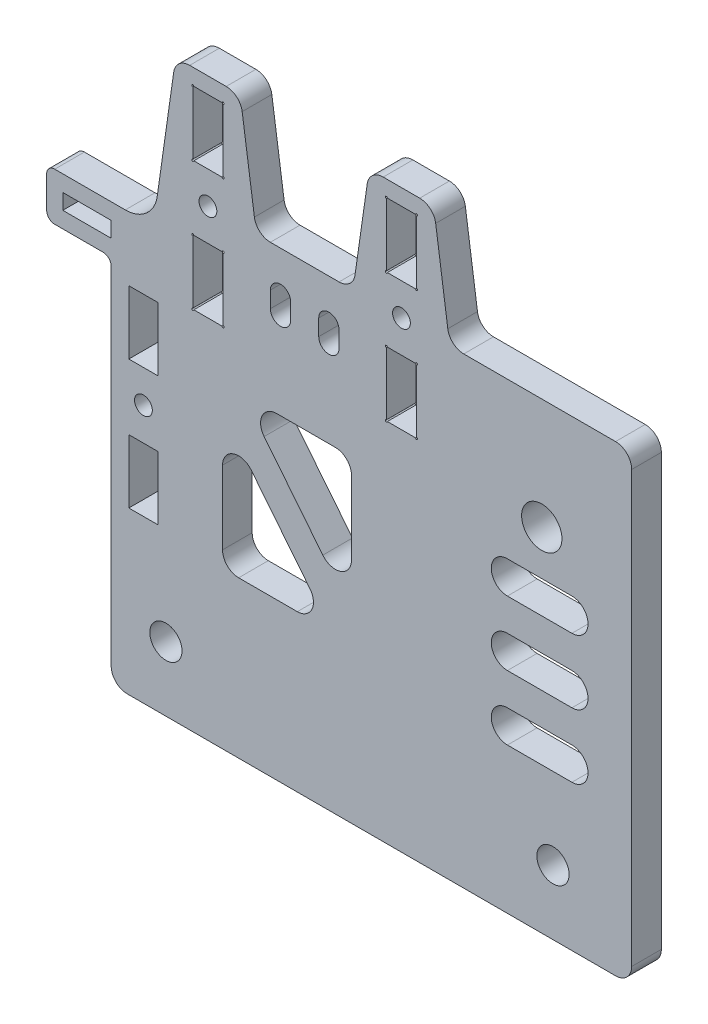
SolidWorks part; units mm, degrees
ref_plane "Front Plane" through (0, 0, 0) normal (0, 0, 1) x (1, 0, 0)
ref_plane "Top Plane" through (0, 0, 0) normal (0, 1, 0) x (1, 0, 0)
ref_plane "Right Plane" through (0, 0, 0) normal (1, 0, 0) x (0, 0, -1)
sketch "Sketch1" plane through (0, 0, 0) normal (0, 0, 1) x (1, 0, 0)
  line L0 (-40.2246, 5.8803) -> (-40.2246, -38.4697) construction
  line L1 (51.8504, -38.4697) -> (-46.5746, -38.4697)
  line L3 (-46.5746, 34.5553) -> (-46.5746, 52.6159)
  line L4 (-46.5746, -38.4697) -> (-46.5746, 34.5553)
  line L5 (51.8504, -38.4697) -> (-46.5746, 34.5553) construction
  line L6 (42.1271, 34.7961) -> (-46.5746, -38.4697) construction
  line L7 (-43.0956, -6.6197) -> (-37.3536, -6.6197)
  line L8 (-43.0956, 18.7803) -> (-37.3536, 18.7803)
  line L9 (-43.0956, 18.7803) -> (-43.0956, 31.2803)
  line L10 (-43.0956, 31.2803) -> (-37.3536, 31.2803)
  line L11 (-37.3536, 18.7803) -> (-37.3536, 31.2803)
  line L12 (-43.0956, 18.7803) -> (-37.3536, 31.2803) construction
  line L13 (-43.0956, 31.2803) -> (-37.3536, 18.7803) construction
  line L14 (-43.0956, -6.6197) -> (-43.0956, 5.8803)
  line L15 (-43.0956, 5.8803) -> (-37.3536, 5.8803)
  line L16 (-37.3536, -6.6197) -> (-37.3536, 5.8803)
  line L17 (-43.0956, -6.6197) -> (-37.3536, 5.8803) construction
  line L18 (-43.0956, 5.8803) -> (-37.3536, -6.6197) construction
  line L19 (-46.5746, 52.6159) -> (51.8504, 52.6159)
  line L20 (51.8504, -25.7697) -> (-46.5746, -25.7697) construction
  line L21 (-40.2246, -0.3697) -> (-40.2246, 25.0303) construction
  line L24 (51.8504, 52.6159) -> (55.8972, 52.6159)
  line L26 (51.8504, -38.4697) -> (55.8972, -38.4697)
  line L27 (55.8972, 52.6159) -> (55.8972, -38.4697)
  circle A0 centre (-35.7968, -25.7697) radius 3.175
  circle A1 centre (40.4032, -25.7697) radius 3.175
  circle A2 centre (-40.2246, 12.3303) radius 1.7526
  point P0 (0, 0)
  point P8 (-40.2246, 25.0303)
  point P14 (-40.2246, -0.3697)
  dimension "D10" = 6.35
  dimension "D13" = 3.5052
  dimension "D1" = 98.425
  dimension "D2" = 73.025
  dimension "D3" = 5.742
  dimension "D4" = 12.5
  dimension "D6" = 6.35
  dimension "D7" = 18.0606
  dimension "D8" = 15.494
  dimension "D12" = 10.7778
  dimension "D5" = 2
  dimension "D11" = 2
extrude "Boss-Extrude1" add sketch "Sketch1" along normal blind 5.842
sketch "Sketch2" plane through (0, 0, 5.842) normal (0, 0, 1) x (1, 0, 0)
  line L0 (55.8972, -38.4697) -> (55.8972, 52.6159) construction
  line L1 (-46.5746, -38.4697) -> (55.8972, -38.4697) construction
  line L2 (33.2912, 44.7153) -> (43.1972, 44.7153) construction
  line L3 (33.2912, -3.5447) -> (43.1972, -3.5447) construction
  line L4 (38.2442, -3.5447) -> (38.2442, 44.7153) construction
  line L6 (48.0747, 0.1423) -> (28.4136, 0.1423)
  line L7 (48.2732, 0.3408) -> (48.2732, 40.8299)
  line L8 (48.0747, 41.0283) -> (28.4136, 41.0283)
  line L9 (28.2152, 0.3408) -> (28.2152, 40.8299)
  line L10 (48.2732, 0.1423) -> (28.2152, 41.0283) construction
  line L11 (48.2732, 41.0283) -> (28.2152, 0.1423) construction
  circle A0 centre (43.1972, -3.5447) radius 1.7526
  circle A1 centre (33.2912, -3.5447) radius 1.7526
  circle A2 centre (43.1972, 44.7153) radius 1.7526
  circle A3 centre (33.2912, 44.7153) radius 1.7526
  arc A4 (48.0747, 0.1423) -> (48.2732, 0.3408) centre (48.2732, 0.1423) ccw
  arc A5 (48.2732, 40.8299) -> (48.0747, 41.0283) centre (48.2732, 41.0283) ccw
  arc A6 (28.2152, 40.8299) -> (28.4136, 41.0283) centre (28.2152, 41.0283) cw
  arc A7 (28.4136, 0.1423) -> (28.2152, 0.3408) centre (28.2152, 0.1423) cw
  point P14 (38.2442, 20.5853)
  dimension "D1" = 3.5052
  dimension "D6" = 0.3969
  dimension "D7" = 0.3969
  dimension "D2" = 12.7
  dimension "D3" = 34.925
  dimension "D4" = 20.058
  dimension "D5" = 40.886
extrude "Cut-Extrude1" [suppressed] cut sketch "Sketch2" against normal through all
sketch "Sketch3" plane through (0, 0, 5.842) normal (0, 0, 1) x (1, 0, 0)
  line L0 (-46.5746, 39.9159) -> (55.8972, 39.9159) construction
  line L1 (-46.5746, 52.6159) -> (-46.5746, -38.4697) construction
  line L2 (55.8972, -38.4697) -> (55.8972, 52.6159) construction
  line L3 (55.8972, 52.6159) -> (-46.5746, 52.6159) construction
  line L4 (7.5909, 46.2659) -> (13.5599, 33.5659) construction
  line L5 (-24.7385, 33.5659) -> (-30.3106, 33.5659)
  line L6 (-24.5401, 33.7644) -> (-24.5401, 46.0675)
  line L7 (-24.7385, 46.2659) -> (-30.3106, 46.2659)
  line L8 (-30.5091, 33.7644) -> (-30.5091, 46.0675)
  line L9 (-24.5401, 33.5659) -> (-30.5091, 46.2659) construction
  line L10 (-8.4746, 52.6159) -> (-8.4746, 39.9159) construction
  line L11 (-24.5401, 46.2659) -> (-30.5091, 33.5659) construction
  line L12 (7.5909, 33.5659) -> (13.5599, 46.2659) construction
  line L13 (13.5599, 33.7644) -> (13.5599, 46.0675)
  line L14 (7.7894, 46.2659) -> (13.3615, 46.2659)
  line L15 (7.5909, 33.7644) -> (7.5909, 46.0675)
  line L16 (7.7894, 33.5659) -> (13.3615, 33.5659)
  arc A0 (-24.7385, 33.5659) -> (-24.5401, 33.7644) centre (-24.5401, 33.5659) ccw
  arc A1 (-30.5091, 33.7644) -> (-30.3106, 33.5659) centre (-30.5091, 33.5659) ccw
  arc A2 (-24.7385, 46.2659) -> (-24.5401, 46.0675) centre (-24.5401, 46.2659) cw
  arc A3 (-30.5091, 46.0675) -> (-30.3106, 46.2659) centre (-30.5091, 46.2659) cw
  arc A4 (13.5599, 46.0675) -> (13.3615, 46.2659) centre (13.5599, 46.2659) ccw
  arc A5 (7.7894, 46.2659) -> (7.5909, 46.0675) centre (7.5909, 46.2659) ccw
  arc A6 (13.5599, 33.7644) -> (13.3615, 33.5659) centre (13.5599, 33.5659) cw
  arc A7 (7.7894, 33.5659) -> (7.5909, 33.7644) centre (7.5909, 33.5659) cw
  point P6 (-27.5246, 39.9159)
  point P7 (-27.5246, 39.9159)
  point P39 (10.5754, 39.9159)
  dimension "D3" = 0.3969
  dimension "D4" = 0.3969
  dimension "D1" = 5.969
  dimension "D2" = 12.7
  dimension "D5" = 12.7
  dimension "D6" = 19.05
  dimension "D9" = 19.05
extrude "Cut-Extrude2" cut sketch "Sketch3" against normal through all
sketch "Sketch4" plane through (0, 0, 5.842) normal (0, 0, 1) x (1, 0, 0)
  line L0 (-30.5091, 39.9159) -> (13.5599, 39.9159) construction
  line L3 (10.5754, 39.9159) -> (10.5754, 65.3159) construction
  line L4 (-8.4746, 39.9159) -> (-8.4746, 46.2659) construction
  line L5 (1.0366, 52.6159) -> (4.2254, 74.8409)
  line L6 (13.3615, 71.6659) -> (7.7894, 71.6659)
  line L7 (13.5599, 71.4675) -> (13.5599, 59.1644)
  line L8 (13.3615, 58.9659) -> (7.7894, 58.9659)
  line L9 (7.5909, 71.4675) -> (7.5909, 59.1644)
  line L10 (13.5599, 71.6659) -> (7.5909, 58.9659) construction
  line L11 (13.5599, 58.9659) -> (7.5909, 71.6659) construction
  line L12 (55.8972, 52.6159) -> (-46.5746, 52.6159) construction
  line L13 (4.2254, 74.8409) -> (16.9254, 74.8409)
  line L14 (16.9254, 74.8409) -> (20.0866, 52.6159)
  line L15 (20.0866, 52.6159) -> (1.0366, 52.6159)
  line L16 (-30.5091, 58.9659) -> (-24.5401, 71.6659) construction
  line L17 (-30.5091, 71.6659) -> (-24.5401, 58.9659) construction
  line L18 (-37.0358, 52.6159) -> (-17.9858, 52.6159)
  line L19 (-33.8746, 74.8409) -> (-37.0358, 52.6159)
  line L20 (-21.1746, 74.8409) -> (-33.8746, 74.8409)
  line L21 (-24.5401, 71.4675) -> (-24.5401, 59.1644)
  line L22 (-30.3106, 58.9659) -> (-24.7385, 58.9659)
  line L23 (-30.5091, 71.4675) -> (-30.5091, 59.1644)
  line L24 (-30.3106, 71.6659) -> (-24.7385, 71.6659)
  line L25 (-17.9858, 52.6159) -> (-21.1746, 74.8409)
  line L26 (13.5599, 33.7644) -> (13.5599, 46.0675) construction
  line L27 (-30.5091, 46.0675) -> (-30.5091, 33.7644) construction
  arc A0 (13.5599, 71.4675) -> (13.3615, 71.6659) centre (13.5599, 71.6659) ccw
  arc A1 (13.3615, 58.9659) -> (13.5599, 59.1644) centre (13.5599, 58.9659) ccw
  arc A2 (7.7894, 58.9659) -> (7.5909, 59.1644) centre (7.5909, 58.9659) cw
  arc A3 (7.5909, 71.4675) -> (7.7894, 71.6659) centre (7.5909, 71.6659) cw
  arc A4 (-24.5401, 71.4675) -> (-24.7385, 71.6659) centre (-24.5401, 71.6659) ccw
  arc A5 (-30.5091, 71.4675) -> (-30.3106, 71.6659) centre (-30.5091, 71.6659) cw
  arc A6 (-24.7385, 58.9659) -> (-24.5401, 59.1644) centre (-24.5401, 58.9659) ccw
  arc A7 (-30.3106, 58.9659) -> (-30.5091, 59.1644) centre (-30.5091, 58.9659) cw
  point P20 (10.5754, 74.8409)
  point P29 (-27.5246, 74.8409)
  dimension "D7" = 0.3969
  dimension "D8" = 0.3969
  dimension "D1" = 25.4
  dimension "D2" = 12.7
  dimension "D3" = 5.969
  dimension "D4" = 9.525
  dimension "D5" = 12.7
  dimension "D6" = 19.05
extrude "Boss-Extrude2" add sketch "Sketch4" against normal up to surface (5.842 mm away) up to face at (10.5754, 39.9159, 0)
fillet "Fillet1" radius 3.175 7 edges at (16.9254, 74.8409, 2.921) (4.2254, 74.8409, 2.921) (-17.9858, 52.6159, 2.921) (-21.1746, 74.8409, 2.921) (-33.8746, 74.8409, 2.921)
sketch "Sketch5" plane through (0, 0, 5.842) normal (0, 0, 1) x (1, 0, 0)
  line L0 (-27.5246, 71.6659) -> (-27.5246, 33.5659) construction
  line L1 (-24.7385, 71.6659) -> (-30.3106, 71.6659) construction
  line L2 (-30.3106, 33.5659) -> (-24.7385, 33.5659) construction
  line L3 (10.5754, 71.6659) -> (10.5754, 33.5659) construction
  line L4 (13.3615, 71.6659) -> (7.7894, 71.6659) construction
  line L5 (7.7894, 33.5659) -> (13.3615, 33.5659) construction
  circle A0 centre (-27.5246, 52.6159) radius 1.7526
  circle A1 centre (10.5754, 52.6159) radius 1.7526
  dimension "D1" = 3.5052
  dimension "D2" = 3.5052
extrude "Cut-Extrude3" cut sketch "Sketch5" against normal through all
sketch "Sketch6" plane through (0, 0, 5.842) normal (0, 0, 1) x (1, 0, 0)
  line L0 (-37.0358, 52.6159) -> (-39.1672, 37.6303)
  line L1 (-34.2626, 72.113) -> (-37.0358, 52.6159) construction
  line L2 (-37.3536, 31.2803) -> (-43.0956, 31.2803) construction
  line L3 (-39.1672, 37.6303) -> (-46.5746, 37.6303)
  line L4 (-46.5746, 52.6159) -> (-46.5746, -38.4697) construction
  line L5 (-46.5746, 37.6303) -> (-46.5746, 52.6159)
  line L6 (-46.5746, 52.6159) -> (-37.0358, 52.6159)
  dimension "D1" = 6.35
extrude "Cut-Extrude4" cut sketch "Sketch6" against normal through all
fillet "Fillet2" radius 3.175 5 edges at (-39.1672, 37.6303, 2.921) (-46.5746, 37.6303, 2.921) (-46.5746, -38.4697, 2.921) (55.8972, 52.6159, 2.921) (55.8972, -38.4697, 2.921)
sketch "Sketch7" [suppressed] plane through (0, 0, 5.842) normal (0, 0, 1) x (1, 0, 0)
  line L0 (6.4764, -22.5947) -> (19.1764, -22.5947) construction
  line L1 (6.4764, -19.4197) -> (19.1764, -19.4197)
  line L2 (6.4764, -25.7697) -> (19.1764, -25.7697)
  line L3 (-43.3996, -38.4697) -> (52.7222, -38.4697) construction
  arc A0 (6.4764, -19.4197) -> (6.4764, -25.7697) centre (6.4764, -22.5947) ccw
  arc A1 (19.1764, -25.7697) -> (19.1764, -19.4197) centre (19.1764, -22.5947) ccw
  point P2 (12.8264, -22.5947)
  dimension "D3" = 3.175
  dimension "D1" = 12.7
  dimension "D2" = 12.7
extrude "Cut-Extrude5" [suppressed] cut sketch "Sketch7" against normal through all
sketch "Sketch8" [suppressed] plane through (0, 0, 5.842) normal (0, 0, 1) x (1, 0, 0)
  line L0 (17.7972, -38.4697) -> (17.7972, 37.7303) construction
  line L1 (-43.3996, -38.4697) -> (52.7222, -38.4697) construction
  line L2 (55.8972, -35.2947) -> (55.8972, 49.4409) construction
  line L3 (14.6222, 5.9803) -> (20.9722, 5.9803) construction
  line L4 (14.6222, 7.5678) -> (20.9722, 7.5678)
  line L5 (14.6222, 4.3928) -> (20.9722, 4.3928)
  line L6 (14.6222, 25.0303) -> (20.9722, 25.0303) construction
  line L7 (14.6222, 26.6178) -> (20.9722, 26.6178)
  line L8 (14.6222, 23.4428) -> (20.9722, 23.4428)
  arc A0 (14.6222, 7.5678) -> (14.6222, 4.3928) centre (14.6222, 5.9803) ccw
  arc A1 (20.9722, 4.3928) -> (20.9722, 7.5678) centre (20.9722, 5.9803) ccw
  arc A2 (14.6222, 26.6178) -> (14.6222, 23.4428) centre (14.6222, 25.0303) ccw
  arc A3 (20.9722, 23.4428) -> (20.9722, 26.6178) centre (20.9722, 25.0303) ccw
  point P8 (17.7972, 5.9803)
  point P17 (17.7972, 25.0303)
  dimension "D2" = 1.5875
  dimension "D1" = 38.1
  dimension "D3" = 6.35
  dimension "D4" = 76.2
  dimension "D5" = 2
  dimension "D6" = 44.45
extrude "Cut-Extrude6" [suppressed] cut sketch "Sketch8" against normal through all
sketch "Sketch9" [suppressed] plane through (0, 0, 5.842) normal (0, 0, 1) x (1, 0, 0)
  line L0 (3.3014, -22.5947) -> (-46.5746, -22.5947) construction
  line L1 (-46.5746, 34.4553) -> (-46.5746, -35.2947) construction
  line L2 (-15.7486, -25.7697) -> (-15.7486, -19.4197) construction
  line L3 (-17.3361, -25.7697) -> (-17.3361, -19.4197)
  line L4 (-14.1611, -25.7697) -> (-14.1611, -19.4197)
  line L5 (-3.0486, -25.7697) -> (-3.0486, -19.4197) construction
  line L6 (-4.6361, -25.7697) -> (-4.6361, -19.4197)
  line L7 (-1.4611, -25.7697) -> (-1.4611, -19.4197)
  arc A0 (6.4764, -19.4197) -> (6.4764, -25.7697) centre (6.4764, -22.5947) ccw construction
  arc A1 (-17.3361, -25.7697) -> (-14.1611, -25.7697) centre (-15.7486, -25.7697) ccw
  arc A2 (-14.1611, -19.4197) -> (-17.3361, -19.4197) centre (-15.7486, -19.4197) ccw
  arc A3 (-4.6361, -25.7697) -> (-1.4611, -25.7697) centre (-3.0486, -25.7697) ccw
  arc A4 (-1.4611, -19.4197) -> (-4.6361, -19.4197) centre (-3.0486, -19.4197) ccw
  point P10 (-15.7486, -22.5947)
  point P18 (-3.0486, -22.5947)
  dimension "D2" = 1.5875
  dimension "D1" = 6.35
  dimension "D3" = 19.05
extrude "Cut-Extrude7" [suppressed] cut sketch "Sketch9" against normal through all
sketch "Sketch10" plane through (0, 0, 5.842) normal (0, 0, 1) x (1, 0, 0)
  line L0 (-20.5876, 24.0409) -> (0.7464, 24.0409)
  line L1 (-30.3106, 33.5659) -> (-24.7385, 33.5659) construction
  line L2 (-24.6536, 18.9584) -> (-24.6536, -7.7091)
  line L3 (-37.3536, 18.7803) -> (-37.3536, 31.2803) construction
  line L4 (0.7464, 24.0409) -> (0.7464, -2.6266)
  line L5 (-3.3196, -7.7091) -> (-24.6536, -7.7091)
  line L7 (-24.6536, 18.9584) -> (-3.3196, -7.7091)
  line L8 (-20.5876, 24.0409) -> (0.7464, -2.6266)
  dimension "D1" = 9.525
  dimension "D2" = 12.7
extrude "Cut-Extrude8" cut sketch "Sketch10" against normal through all
fillet "Fillet3" radius 3.175 6 edges at (0.7464, 24.0409, 2.921) (0.7464, -2.6266, 2.921) (-20.5876, 24.0409, 2.921) (-24.6536, 18.9584, 2.921) (-24.6536, -7.7091, 2.921) (-3.3196, -7.7091, 2.921)
sketch "Sketch11" plane through (0, 0, 5.842) normal (0, 0, 1) x (1, 0, 0)
  line L0 (55.8972, -35.2947) -> (55.8972, 49.4409) construction
  line L1 (52.7222, 52.6159) -> (22.842, 52.6159) construction
  circle A0 centre (36.8472, 27.2159) radius 1.92
  circle A1 centre (40.4472, 2.5659) radius 1.92
  dimension "D1" = 3.84
  dimension "D2" = 3.84
  dimension "D3" = 3.6
  dimension "D4" = 24.65
  dimension "D5" = 19.05
  dimension "D6" = 25.4
extrude "Cut-Extrude9" [suppressed] cut sketch "Sketch11" against normal through all
sketch "Sketch12" plane through (0, 0, 5.842) normal (0, 0, 1) x (1, 0, 0)
  line L0 (-24.5401, 42.8787) -> (7.5909, 42.8787) construction
  line L1 (-24.5401, 33.7644) -> (-24.5401, 46.0675) construction
  line L2 (7.5909, 46.0675) -> (7.5909, 33.7644) construction
  line L3 (-8.4746, 52.6159) -> (-8.4746, 42.8787) construction
  line L4 (-1.7153, 52.6159) -> (-15.2338, 52.6159) construction
  line L5 (-3.7121, 41.2912) -> (-3.7121, 44.4662) construction
  line L6 (-5.7121, 41.2912) -> (-5.7121, 44.4662)
  line L7 (-1.7121, 41.2912) -> (-1.7121, 44.4662)
  line L8 (-13.2371, 41.2912) -> (-13.2371, 44.4662) construction
  line L9 (-11.2371, 41.2912) -> (-11.2371, 44.4662)
  line L10 (-15.2371, 41.2912) -> (-15.2371, 44.4662)
  arc A0 (-5.7121, 41.2912) -> (-1.7121, 41.2912) centre (-3.7121, 41.2912) ccw
  arc A1 (-1.7121, 44.4662) -> (-5.7121, 44.4662) centre (-3.7121, 44.4662) ccw
  arc A2 (-11.2371, 41.2912) -> (-15.2371, 41.2912) centre (-13.2371, 41.2912) cw
  arc A3 (-15.2371, 44.4662) -> (-11.2371, 44.4662) centre (-13.2371, 44.4662) cw
  point P12 (-3.7121, 42.8787)
  point P19 (-13.2371, 42.8787)
  dimension "D2" = 2
  dimension "D1" = 3.175
  dimension "D3" = 4.7625
extrude "Cut-Extrude10" cut sketch "Sketch12" against normal through all
sketch "Sketch14" plane through (0, 0, 5.842) normal (0, 0, 1) x (1, 0, 0)
  line L0 (-46.5746, 37.6303) -> (-55.1563, 37.6303) construction
  line L1 (-43.3996, 37.6303) -> (-41.9226, 37.6303) construction
  line L2 (-46.5746, 34.4553) -> (-46.5746, -35.2947) construction
  line L3 (-46.5746, 37.6303) -> (-56.0996, 37.6303)
  line L4 (-42.6611, 37.6303) -> (-42.6611, 34.4553)
  line L5 (-42.6611, 34.4553) -> (-59.2746, 34.4553)
  line L6 (-59.2746, 37.6303) -> (-59.2746, 34.4553)
  line L7 (-59.2746, 37.6303) -> (-59.2746, 43.8533)
  line L8 (-46.5746, 40.6783) -> (-56.0996, 40.6783)
  line L9 (-46.5746, 40.6783) -> (-46.5746, 37.6303)
  line L10 (-46.5746, 37.6303) -> (-56.0996, 37.6303) construction
  line L11 (-56.0996, 40.6783) -> (-56.0996, 37.6303)
  line L12 (-46.5746, 40.6783) -> (-56.0996, 37.6303) construction
  line L13 (-46.5746, 37.6303) -> (-56.0996, 40.6783) construction
  line L14 (-59.2746, 43.8533) -> (-38.2821, 43.8533)
  line L15 (-34.2626, 72.113) -> (-38.7792, 40.3582) construction
  line L16 (-42.6611, 37.6303) -> (-41.9226, 37.6303)
  line L17 (-38.2821, 43.8533) -> (-38.7792, 40.3582)
  arc A0 (-41.9226, 37.6303) -> (-38.7792, 40.3582) centre (-41.9226, 40.8053) ccw construction
  arc A1 (-41.9226, 37.6303) -> (-38.7792, 40.3582) centre (-41.9226, 40.8053) ccw
  point P9 (-51.3371, 39.1543)
  dimension "D1" = 3.175
  dimension "D2" = 12.7
  dimension "D3" = 3.048
  dimension "D4" = 9.525
  dimension "D5" = 3.175
  dimension "D6" = 3.175
extrude "Boss-Extrude3" add sketch "Sketch14" against normal up to surface (5.842 mm away) contours L16 A1 L17 L14 L7 L6 L5 L4 region at (-42.8911, 36.0428, 5.842) up to face at (-13.2371, 42.8787, 0)
fillet "Fillet4" radius 1.5875 3 edges at (-59.2746, 43.8533, 2.921) (-59.2746, 34.4553, 2.921) (-46.5746, 34.4553, 2.921)
fillet "Fillet5" radius 6.35 1 edges at (-38.2821, 43.8533, 2.921)
sketch "Sketch15" plane through (0, 0, 5.842) normal (0, 0, 1) x (1, 0, 0)
  line L0 (55.8972, -35.2947) -> (55.8972, 49.4409) construction
  line L1 (-43.3996, -38.4697) -> (52.7222, -38.4697) construction
  circle A0 centre (38.1972, 30.7553) radius 3.9687
  dimension "D1" = 7.9375
  dimension "D2" = 17.7
  dimension "D3" = 69.225
extrude "Cut-Extrude11" cut sketch "Sketch15" against normal through all
sketch "Sketch16" plane through (0, 0, 5.842) normal (0, 0, 1) x (1, 0, 0)
  line L0 (37.7821, 52.6159) -> (37.7821, -38.4697) construction
  line L1 (52.7222, 52.6159) -> (22.842, 52.6159) construction
  line L2 (-43.3996, -38.4697) -> (52.7222, -38.4697) construction
  line L3 (31.4321, -6.5927) -> (44.1321, -6.5927) construction
  line L4 (31.4321, -3.4177) -> (44.1321, -3.4177)
  line L5 (31.4321, -9.7677) -> (44.1321, -9.7677)
  line L6 (31.4321, 6.1073) -> (44.1321, 6.1073) construction
  line L7 (31.4321, 9.2823) -> (44.1321, 9.2823)
  line L8 (31.4321, 2.9323) -> (44.1321, 2.9323)
  line L9 (31.4321, 18.8073) -> (44.1321, 18.8073) construction
  line L10 (31.4321, 21.9823) -> (44.1321, 21.9823)
  line L11 (31.4321, 15.6323) -> (44.1321, 15.6323)
  arc A0 (31.4321, -3.4177) -> (31.4321, -9.7677) centre (31.4321, -6.5927) ccw
  arc A1 (44.1321, -9.7677) -> (44.1321, -3.4177) centre (44.1321, -6.5927) ccw
  arc A2 (31.4321, 9.2823) -> (31.4321, 2.9323) centre (31.4321, 6.1073) ccw
  arc A3 (44.1321, 2.9323) -> (44.1321, 9.2823) centre (44.1321, 6.1073) ccw
  arc A4 (31.4321, 21.9823) -> (31.4321, 15.6323) centre (31.4321, 18.8073) ccw
  arc A5 (44.1321, 15.6323) -> (44.1321, 21.9823) centre (44.1321, 18.8073) ccw
  point P8 (37.7821, -6.5927)
  point P17 (37.7821, 6.1073)
  point P24 (37.7821, 18.8073)
  dimension "D2" = 3.175
  dimension "D1" = 12.7
  dimension "D3" = 31.877
  dimension "D4" = 3
extrude "Cut-Extrude12" cut sketch "Sketch16" against normal through all
